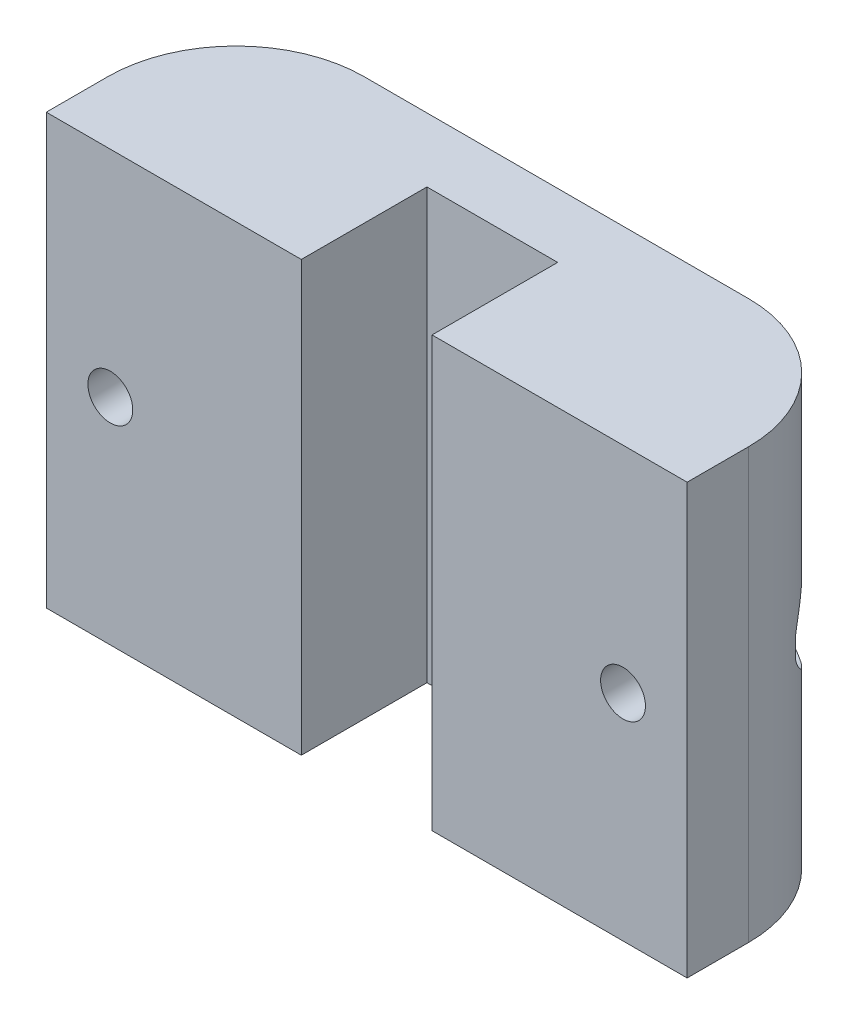
SolidWorks part; units mm, degrees
ref_plane "Спереди" through (0, 0, 0) normal (0, 0, 1) x (1, 0, 0)
ref_plane "Сверху" through (0, 0, 0) normal (0, 1, 0) x (1, 0, 0)
ref_plane "Справа" through (0, 0, 0) normal (1, 0, 0) x (0, 0, -1)
sketch "Sketch2" plane through (0, 0, 0) normal (0, 0, 1) x (1, 0, 0)
  line L0 (20, 0) -> (-20, 0) construction
  line L1 (25, -16.75) -> (-25, -16.75)
  line L2 (25, -16.75) -> (25, 16.75)
  line L3 (25, 16.75) -> (-25, 16.75)
  line L4 (-25, -16.75) -> (-25, 16.75)
  line L5 (25, -16.75) -> (-25, 16.75) construction
  line L6 (25, 16.75) -> (-25, -16.75) construction
  circle A0 centre (-20, 0) radius 1.75
  circle A1 centre (20, 0) radius 1.75
  point P0 (0, 0)
  point P9 (0, 0)
  dimension "D4" = 3.5
  dimension "D1" = 33.5
  dimension "D2" = 50
  dimension "D3" = 40
extrude "Boss-Extrude1" add sketch "Sketch2" along normal blind 5
sketch "Sketch5" plane through (0, -16.75, 0) normal (0, -1, 0) x (1, 0, 0)
  line L0 (-25, 5) -> (-25, 14.8)
  line L1 (-25, 5) -> (25, 5) construction
  line L2 (-25, 14.8) -> (-5.1, 14.8)
  line L3 (-5.1, 14.8) -> (-5.1, 5)
  line L4 (-5.1, 5) -> (5.1, 5)
  line L5 (5.1, 5) -> (5.1, 14.8)
  line L6 (5.1, 14.8) -> (25, 14.8)
  line L7 (25, 14.8) -> (25, 5)
  line L8 (25, 5) -> (-25, 5) construction
  line L9 (-25, 0) -> (25, 0) construction
  line L10 (0, 5) -> (0, 0) construction
  line L11 (25, 5) -> (25, 0) construction
  arc A0 (-25, 5) -> (25, 5) centre (0, 65) ccw
  point P15 (0, 0)
  dimension "D1" = 10.2
  dimension "D3" = 9.8
extrude "Boss-Extrude2" add sketch "Sketch5" against normal up to surface (33.5 mm away) up to face at (0, 16.75, 2.5)
sketch "Sketch6" plane through (0, 0, 0) normal (0, 0, -1) x (-1, 0, 0)
  circle A0 centre (20, 0) radius 1.75
  circle A1 centre (-20, 0) radius 1.75
  circle A2 centre (-20, 0) radius 1.75 construction
extrude "Cut-Extrude1" cut sketch "Sketch6" against normal through all
fillet "Fillet1" radius 10 2 edges at (25, 0, 0) (-25, 0, 0)
sketch "Sketch7" plane through (0, 0, 0) normal (0, 0, -1) x (-1, 0, 0)
  circle A0 centre (20, 0) radius 3.75
  circle A1 centre (-20, 0) radius 3.75
  dimension "D1" = 7.5
extrude "Cut-Extrude2" cut sketch "Sketch7" against normal blind 5
sketch "Sketch8" plane through (0, 0, 0) normal (0, 0, -1) x (-1, 0, 0)
  line L0 (15, -1.75) -> (-15, -1.75) construction
  line L1 (15, -16.75) -> (15, 16.75) construction
  line L2 (-15, 16.75) -> (-15, -16.75) construction
  line L3 (15, -16.75) -> (-15, -16.75) construction
  text T0 "<b>35mm</b>\r\n<b>screws</b>" font "Arial" height 5
  dimension "D1" = 15
extrude "Boss-Extrude3" add sketch "Sketch8" along normal blind 0.5
